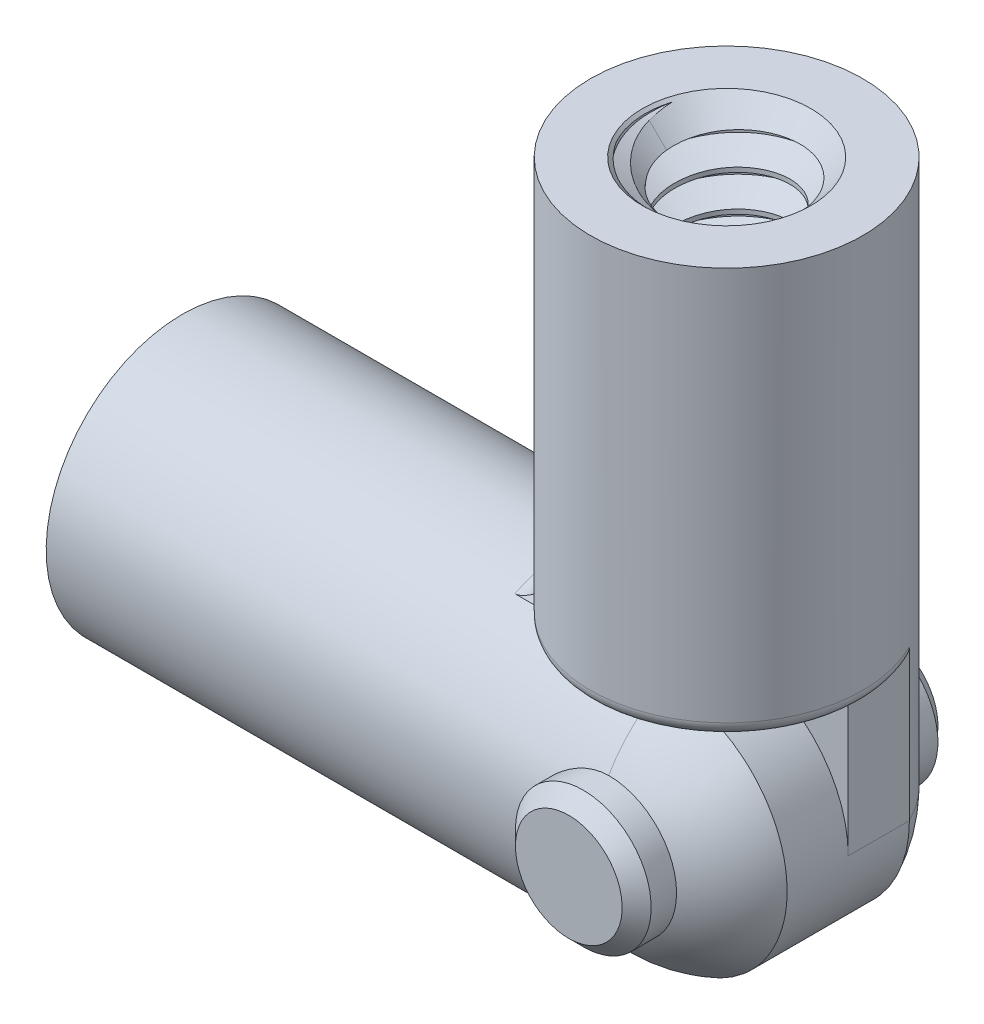
SolidWorks part; units mm, degrees
ref_plane "Front Plane" through (0, 0, 0) normal (0, 0, 1) x (1, 0, 0)
ref_plane "Top Plane" through (0, 0, 0) normal (0, 1, 0) x (1, 0, 0)
ref_plane "Right Plane" through (0, 0, 0) normal (1, 0, 0) x (0, 0, -1)
sketch "Sketch1" plane through (0, 0, 0) normal (0, 0, 1) x (1, 0, 0)
  line L0 (0, 0) -> (-9.525, 0) construction
  line L1 (-9.525, 2.3812) -> (-9.525, -2.3813) construction
  line L2 (-5.5563, 1.4224) -> (-5.5562, -1.4224) construction
  line L3 (-5.5562, -1.4224) -> (-9.525, -1.4224) construction
  line L4 (-5.5563, 1.4224) -> (-9.525, 1.4224) construction
  line L5 (-9.525, 2.3812) -> (-9.525, 1.4224)
  line L6 (-9.525, 1.4224) -> (-5.5563, 1.4224)
  line L7 (-5.5563, 1.4224) -> (-5.5562, 0)
  line L8 (-5.5562, 0) -> (2.3812, 0)
  line L9 (-9.525, 2.3812) -> (0, 2.3812)
  arc A0 (0, 2.3812) -> (2.3812, 0) centre (0, 0) cw
  point P7 (-5.5562, 0)
  dimension "A" = 9.525
  dimension "OD" = 4.7625
  dimension "Screw Size" = 2.8448
  dimension "C1" = 3.9688
revolve "Revolve1" add sketch "Sketch1" angle 360 about L0
sketch "Sketch2" plane through (0, 0, 0) normal (0, 0, 1) x (1, 0, 0)
  line L1 (-2.3812, 2.3812) -> (2.3812, 2.3812)
  line L2 (-2.3812, 2.3812) -> (-2.3812, -2.3813)
  line L3 (-2.3812, -2.3813) -> (2.3812, -2.3813)
  line L4 (2.3812, 2.3812) -> (2.3812, -2.3813)
extrude "Extrude1" cut sketch "Sketch2" against normal through all
sketch "Sketch4" plane through (0, 0, 0) normal (0, 0, -1) x (-1, 0, 0)
  line L1 (2.3812, 2.3812) -> (2.3812, -2.3813) construction
  line L2 (2.3812, 2.3812) -> (-2.3812, 2.3812) construction
  line L3 (2.3812, -2.3813) -> (-2.3812, -2.3813) construction
  line L5 (2.3812, 2.3812) -> (0, 2.3812)
  line L6 (0, -2.1272) -> (2.1272, -2.1273)
  line L7 (2.1272, -2.1273) -> (2.1272, 2.1272)
  line L8 (2.1272, 2.1272) -> (0, 2.1272)
  line L9 (0, -2.1272) -> (2.3812, -2.1272)
  line L10 (2.3812, -2.3813) -> (2.3812, -2.1272)
  line L11 (2.3812, 2.1272) -> (0, 2.1272)
  line L12 (2.3812, -2.3813) -> (0, -2.3812)
  line L13 (2.3812, 2.1272) -> (2.3812, 2.3812)
  arc A0 (0, 2.3812) -> (0, -2.3812) centre (0, 0) ccw construction
  arc A1 (0, 2.3812) -> (0, -2.3812) centre (0, 0) ccw
  arc A2 (0, 2.1272) -> (0, -2.1272) centre (0, 0) ccw
  arc A3 (0, 2.1272) -> (0, -2.1272) centre (0, 0) ccw
  dimension "D1" = 0.254
extrude "Extrude2" cut sketch "Sketch4" against normal through all
fillet "Fillet1" radius 0.254 1 edges at (-2.3812, 0, -2.3812) type face fillet first side face at (-2.3812, 0, -0.3278) second side face at (-1.1906, 0, 0.5351)
sketch "Sketch6" plane through (-9.525, 0, 0) normal (-1, 0, 0) x (0, 0, 1)
  line L0 (0, 0) -> (-1.4224, 0) construction
  line L1 (0, 0) -> (-1.0058, 1.0058) construction
  circle A0 centre (0, 0) radius 1.4224 construction
  circle A1 centre (0, 0) radius 1.4224
  dimension "D1" = 45
curve "Helix/Spiral1" pitch 0.635 height 4.6037 radius 1.4224 centre (-9.525, 0, 0) axis (1, 0, 0) start towards (0, 1, 0) parameters "Pitch"=0.635
sketch "Sketch7" plane through (0, 0, 0) normal (0, 0, 1) x (1, 0, 0)
  line L0 (-10.0806, 1.4224) -> (-9.525, 1.4224)
  line L1 (-9.525, 1.4224) -> (-9.7631, 1.01)
  line L2 (-9.7631, 1.01) -> (-9.8425, 1.01)
  line L3 (-9.8425, 1.01) -> (-10.0806, 1.4224)
  line L4 (-9.8028, 1.01) -> (-9.8028, 1.4224) construction
  line L5 (-9.9616, 1.2162) -> (-9.6441, 1.2162) construction
  dimension "D1" = 60
  dimension "D2" = 0.0794
  dimension "D3" = 0.3175
sweep "Sweep2" add profiles "Sketch7" path "Helix/Spiral1"
sketch "Sketch8" plane through (-9.525, 0, 0) normal (-1, 0, 0) x (0, 0, 1)
  circle A2 centre (0, 0) radius 1.4732
  circle A3 centre (0, 0) radius 1.4732
  dimension "D1" = 0.0508
extrude "Extrude5" cut sketch "Sketch8" along normal through all and the other way blind 3.9688 draft 45
sketch "Sketch10" plane through (0, 0, 0) normal (0, 0, 1) x (1, 0, 0)
  line L0 (0, 9.525) -> (2.3813, 9.525)
  line L1 (2.3813, 9.525) -> (2.3813, 0)
  line L2 (0, 9.525) -> (0, -2.3813)
  line L4 (-1.4224, 9.525) -> (1.4224, 9.525) construction
  line L5 (-1.4224, 9.525) -> (-1.4224, 5.5563) construction
  line L6 (-1.4224, 5.5563) -> (1.4224, 5.5563) construction
  line L7 (1.4224, 9.525) -> (1.4224, 5.5563) construction
  arc A0 (2.3813, 0) -> (0, -2.3813) centre (0, 0) cw
  dimension "D1" = 3.9688
  dimension "B" = 9.525
  dimension "D2" = 2.3813
  dimension "D3" = 2.8448
revolve "Revolve2" add sketch "Sketch10" angle 360 about L2
sketch "Sketch11" plane through (0, 9.525, 0) normal (0, 1, 0) x (1, 0, 0)
  circle A0 centre (0, 0) radius 1.4224
  dimension "D1" = 2.8448
extrude "Extrude7" cut sketch "Sketch11" against normal blind 3.9688
sketch "Sketch17" plane through (0, 0, 0) normal (1, 0, 0) x (0, 0, -1)
  line L1 (-1.4224, 9.525) -> (1.4224, 9.525)
  line L2 (-1.4224, 9.525) -> (-1.4224, 5.5563)
  line L3 (-1.4224, 5.5563) -> (1.4224, 5.5563)
  line L4 (1.4224, 9.525) -> (1.4224, 5.5563)
  dimension "D1" = 2.8448
sketch "Sketch12" plane through (0, 0, 0) normal (0, 0, 1) x (1, 0, 0)
  line L1 (-2.3813, 2.3813) -> (2.3813, 2.3813)
  line L2 (-2.3813, 2.3813) -> (-2.3813, -2.3813)
  line L3 (-2.3813, -2.3813) -> (2.3813, -2.3813)
  line L4 (2.3813, 2.3813) -> (2.3813, -2.3813)
  arc A0 (0, -2.3813) -> (2.3813, 0) centre (0, 0) ccw construction
extrude "Extrude8" cut sketch "Sketch12" along normal through all
sketch "Sketch13" plane through (0, 0, 0) normal (0, 0, 1) x (1, 0, 0)
  line L3 (-2.1273, 2.3813) -> (-2.3813, 2.3813)
  line L6 (-2.1273, 2.1273) -> (-2.1273, 0)
  line L7 (2.1273, 0) -> (2.1273, 2.1273)
  line L8 (2.1273, 2.1273) -> (-2.1273, 2.1273)
  line L9 (-2.1273, 2.3813) -> (-2.1273, 0)
  line L10 (2.1273, 0) -> (2.1273, 2.3813)
  line L11 (-2.3813, 2.3813) -> (-2.3813, 0)
  line L12 (2.3813, 0) -> (2.3813, 2.3813)
  line L13 (2.3813, 2.3813) -> (-2.3813, 2.3813)
  line L14 (-2.3813, 2.3813) -> (-2.3813, 0)
  line L15 (2.3813, 0) -> (2.3813, 2.3813)
  line L16 (2.3813, 2.3813) -> (2.1273, 2.3813)
  arc A2 (-2.1273, 0) -> (2.1273, 0) centre (0, 0) ccw
  arc A3 (-2.1273, 0) -> (2.1273, 0) centre (0, 0) ccw
  arc A4 (-2.3813, 0) -> (2.3813, 0) centre (0, 0) ccw
  arc A5 (-2.3813, 0) -> (2.3813, 0) centre (0, 0) ccw
  dimension "D1" = 0.254
  dimension "D2" = 0
extrude "Extrude10" cut sketch "Sketch13" against normal through all
fillet "Fillet2" radius 0.254 1 edges at (0, 2.3813, 2.3812) type face fillet first side face at (0, 2.3813, 0.3278) second side face at (-2.3812, 9.525, 0)
sketch "Sketch14" plane through (0, 9.525, 0) normal (0, 1, 0) x (1, 0, 0)
  circle A0 centre (0, 0) radius 1.4224 construction
  circle A1 centre (0, 0) radius 1.4224
curve "Helix/Spiral2" pitch 0.635 height 4.6037 radius 1.4224 left hand yes centre (0, 9.525, 0) axis (0, -1, 0) start towards (-1, 0, 0)
sketch "Sketch15" plane through (0, 0, 0) normal (0, 0, 1) x (1, 0, 0)
  line L0 (-1.4224, 10.0806) -> (-1.4224, 9.525)
  line L1 (-1.4224, 9.525) -> (-1.01, 9.7631)
  line L2 (-1.01, 9.7631) -> (-1.01, 9.8425)
  line L3 (-1.01, 9.8425) -> (-1.4224, 10.0806)
  line L4 (-1.01, 9.8028) -> (-1.4224, 9.8028) construction
  line L5 (-1.2162, 9.6441) -> (-1.2162, 9.9616) construction
  dimension "D1" = 60
  dimension "D2" = 0.3175
  dimension "D3" = 0.0794
sweep "Sweep3" add profiles "Sketch15" path "Helix/Spiral2"
sketch "Sketch16" plane through (0, 9.525, 0) normal (0, 1, 0) x (1, 0, 0)
  circle A2 centre (0, 0) radius 1.4732
  circle A3 centre (0, 0) radius 1.4732
  dimension "D1" = 0.0508
extrude "Extrude11" cut sketch "Sketch16" along normal through all and the other way through all draft 45
sketch "Sketch9" plane through (0, 0, 0) normal (0, 0, -1) x (-1, 0, 0)
  circle A1 centre (0, 0) radius 1.1875
  dimension "D1" = 2.3749
extrude "Extrude6" add sketch "Sketch9" against normal mid plane 5.5245
chamfer "Chamfer1" distance 0.254 angle 45 2 edges at (-1.1875, 0, 2.7623) (-1.1875, 0, -2.7623)
equation "\"D2@Sketch7\" = \"Pitch@Helix/Spiral1\"*.125"
equation "\"D3@Sketch7\" = \"Pitch@Helix/Spiral1\"*.5"
equation "\"D3@Helix/Spiral1\" = \"C1@Sketch1\"+\"Pitch@Helix/Spiral1\""
equation "\"D2@Extrude5\" = \"C1@Sketch1\""
equation "\"D1@Extrude6\" = \"OD@Sketch1\"+.030"
equation "\"D2@Sketch10\" = \"OD@Sketch1\"/2"
equation "\"D1@Sketch11\" = \"Screw Size@Sketch1\""
equation "\"D4@Helix/Spiral2\" = \"Pitch@Helix/Spiral1\""
equation "\"D2@Sketch15\" = \"Pitch@Helix/Spiral1\"*.50"
equation "\"D3@Sketch15\" = \"Pitch@Helix/Spiral1\"*.125"
equation "\"D3@Helix/Spiral2\" = \"C2@Extrude7\"+\"D4@Helix/Spiral2\""
equation "\"D1@Sketch10\" = \"C2@Extrude7\""
equation "\"D3@Sketch10\" = \"Screw Size@Sketch1\""
equation "\"D1@Sketch17\" = \"Screw Size@Sketch1\""
